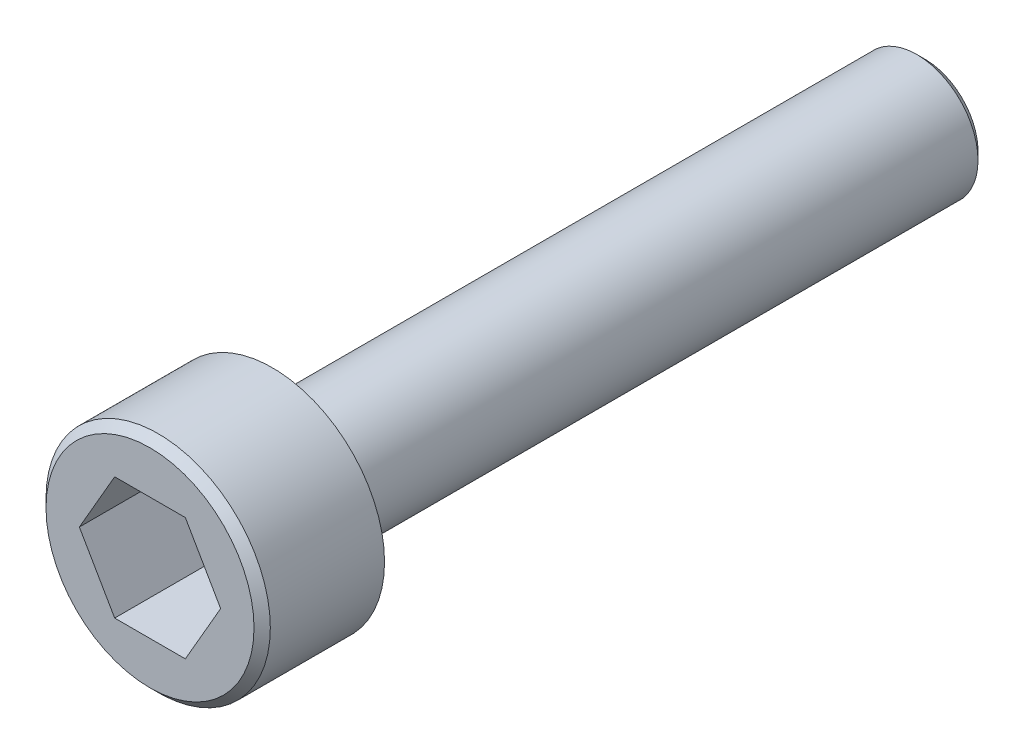
SolidWorks part; units mm, degrees
ref_plane "Plane1" through (0, 0, 0) normal (0, 0, 1) x (1, 0, 0)
ref_plane "Plane2" through (0, 0, 0) normal (0, 1, 0) x (1, 0, 0)
ref_plane "Plane3" through (0, 0, 0) normal (1, 0, 0) x (0, 0, -1)
sketch "S" plane through (0, 0, 0) normal (0, 1, 0) x (-1, 0, 0)
  line L0 (0, 20) -> (0, -24.6742) construction
  line L1 (0, 0) -> (2.75, 0)
  line L2 (22.2887, -12) -> (-19.2648, -12) construction
  line L3 (2.75, 0) -> (2.75, -3)
  line L4 (2.75, -3) -> (1.5, -3)
  line L5 (1.5, -3) -> (1.5, -19)
  line L7 (1.5, -19) -> (0, -19)
  line L8 (0, -19) -> (0, 0)
  dimension "A" = 5.5
  dimension "M" = 3
  dimension "E" = 3
  dimension "L" = 16
  dimension "PS1" = 7
revolve "D" add sketch "S" angle 360 about L0
cosmetic thread "ねじ山1" parameters "PS1"=6.8, "PD1"=3.3
chamfer "面取り1" distance 0.2 angle 45 1 edges at (2.75, 0, 0)
chamfer "面取り2" distance 0.2 angle 45 1 edges at (1.5, 0, -19)
sketch "ｽｹｯﾁ2" plane through (0, 0, 0) normal (0, 0, 1) x (0, 1, 0)
  line L0 (0, 1.7321) -> (0, 0) construction
  line L1 (0, 1.7321) -> (1.5, 0.866)
  line L2 (1.5, 0.866) -> (1.5, -0.866)
  line L3 (-1.5, 0.866) -> (-1.5, -0.866)
  line L4 (0, 1.7321) -> (-1.5, 0.866)
  line L5 (0, -1.7321) -> (-1.5, -0.866)
  line L6 (0, -1.7321) -> (1.5, -0.866)
  line L7 (-30, 0) -> (30, 0) construction
  point P12 (-1.5, 0)
  point P13 (1.5, 0)
  dimension "B" = 3
extrude "ｶｯﾄ - 押し出し1" cut sketch "ｽｹｯﾁ2" against normal blind 2.4
sketch "ｽｹｯﾁ3" plane through (0, 0, 0) normal (0, 1, 0) x (1, 0, 0)
  line L0 (-1.8321, 0) -> (0, 0)
  line L1 (0, 18.8) -> (0, 19) construction
  line L2 (0, 30.0783) -> (0, -8.7127) construction
  line L4 (-2.55, 0) -> (2.55, 0) construction
  line L5 (0, 0) -> (0, 3.4)
  line L8 (-1.8321, 0) -> (-1.8321, 2.3423)
  line L9 (-1.8321, 2.3423) -> (0, 3.4)
  line L10 (-1.7321, 2.4) -> (-1.7321, 0) construction
  dimension "D1" = 60
  dimension "D2" = 0.1
revolve "ｶｯﾄ - 回転1" cut sketch "ｽｹｯﾁ3" angle 360 about L2
sketch "ｽｹｯﾁ4" plane through (0, 0, 0) normal (0, 0, 1) x (1, 0, 0)
  line L6 (-1.7321, 0) -> (-0.866, 1.5)
  line L7 (-0.866, 1.5) -> (0.866, 1.5)
  line L8 (1.7321, 0) -> (0.866, 1.5)
  line L9 (1.7321, 0) -> (0.866, -1.5)
  line L10 (-0.866, -1.5) -> (0.866, -1.5)
  line L11 (-1.7321, 0) -> (-0.866, -1.5)
  line L12 (-1.7321, 0) -> (-0.866, 1.5)
  line L13 (-0.866, 1.5) -> (0.866, 1.5)
  line L14 (1.7321, 0) -> (0.866, 1.5)
  line L15 (1.7321, 0) -> (0.866, -1.5)
  line L16 (-0.866, -1.5) -> (0.866, -1.5)
  line L17 (-1.7321, 0) -> (-0.866, -1.5)
  circle A1 centre (0, 0) radius 1.8321 construction
  circle A2 centre (0, 0) radius 1.8321
  dimension "D1" = 0
extrude "ﾎﾞｽ - 押し出し2" add sketch "ｽｹｯﾁ4" against normal up to next
ref_plane "合致面1" through (0, 0, 0) normal (0, 0, 1) x (1, 0, 0)
ref_plane "合致面2" through (0, 0, -3) normal (0, 0, -1) x (-1, 0, 0)
sketch "つば輪郭" plane through (0, 0, 0) normal (0, 0, 1) x (1, 0, 0)
  circle A2 centre (0, 0) radius 2.75 construction
  circle A3 centre (0, 0) radius 2.75
sketch "ピン輪郭" plane through (0, 0, -3) normal (0, 0, -1) x (-1, 0, 0)
  circle A0 centre (0, 0) radius 1.5 construction
  circle A1 centre (0, 0) radius 1.5
ref_axis "軸1" through (0, 0, 70) along (0, 0, -1)
sketch "ねじ下穴" plane through (0, 0, -3) normal (0, 0, -1) x (-1, 0, 0)
  circle A0 centre (0, 0) radius 1.65
  dimension "D1" = 3.3
